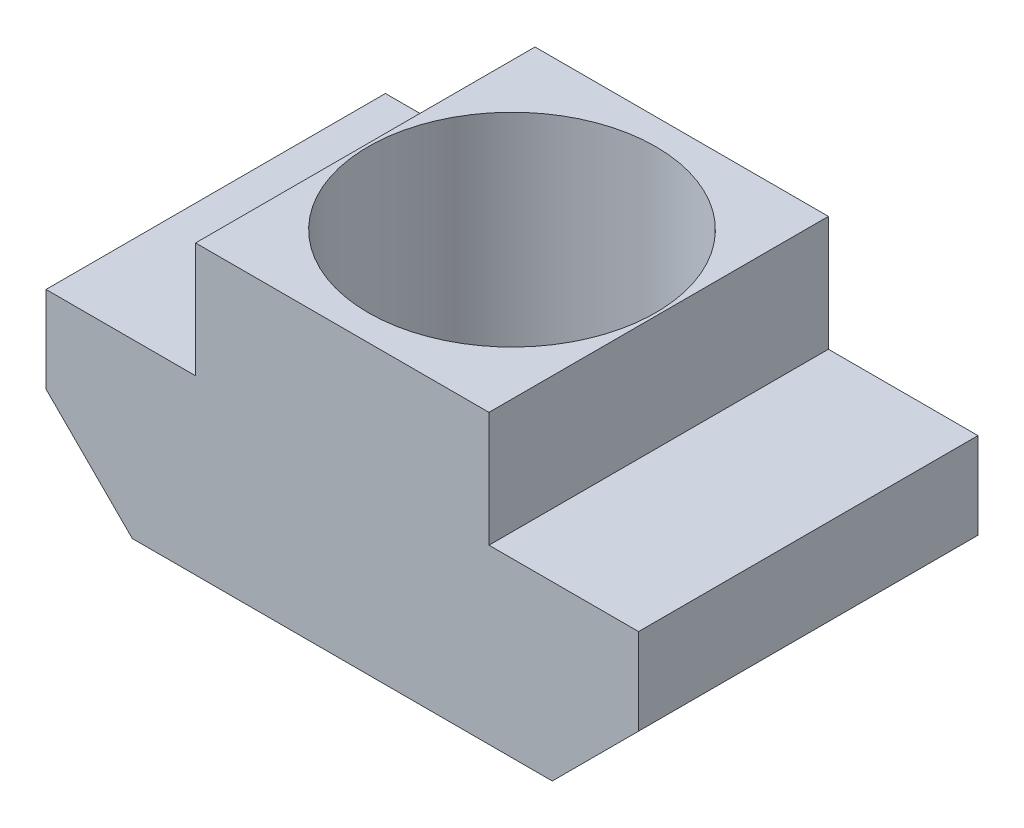
SolidWorks part; units mm, degrees
ref_plane "前视基准面" through (0, 0, 0) normal (0, 0, 1) x (1, 0, 0)
ref_plane "上视基准面" through (0, 0, 0) normal (0, 1, 0) x (1, 0, 0)
ref_plane "右视基准面" through (0, 0, 0) normal (1, 0, 0) x (0, 0, -1)
sketch "草图1" plane through (0, 0, 0) normal (0, 1, 0) x (1, 0, 0)
  line L1 (5.15, 2.95) -> (-5.15, 2.95)
  line L2 (5.15, 2.95) -> (5.15, -2.95)
  line L3 (5.15, -2.95) -> (-5.15, -2.95)
  line L4 (-5.15, 2.95) -> (-5.15, -2.95)
  line L5 (2.55, 2.95) -> (-2.55, 2.95)
  line L6 (2.55, 2.95) -> (2.55, -2.95)
  line L7 (2.55, -2.95) -> (-2.55, -2.95)
  line L8 (-2.55, 2.95) -> (-2.55, -2.95)
  line L9 (2.55, 2.95) -> (-2.55, -2.95) construction
  line L10 (2.55, -2.95) -> (-2.55, 2.95) construction
  circle A0 centre (0, 0) radius 2.5
  point P0 (0, 0)
  dimension "D3" = 5.9
  dimension "D1" = 10.3
  dimension "D2" = 5.9
  dimension "D4" = 5.1
extrude "凸台-拉伸3" add sketch "草图1" along normal blind 3 contours L8 L1 L4 L3 | L1 L6 L3 L2 region at (3.85, 0, 0) region at (-3.85, 0, 0)
extrude "凸台-拉伸4" add sketch "草图1<3>" along normal blind 5 contours L1 L8 L3 L6 A0 region at (2.5422, 0, 0)
sketch "草图1<3>" plane through (0, 0, 0) normal (0, 1, 0) x (1, 0, 0) same geometry as "草图1"
sketch "草图2" plane through (0, 0, 2.95) normal (0, 0, 1) x (1, 0, 0)
  line L0 (-5.15, 3) -> (-5.15, 0) construction
  line L1 (-5.15, 1.5) -> (-3.65, 0)
  line L2 (5.15, 0) -> (-5.15, 0) construction
  line L3 (5.15, 1.5) -> (3.65, 0)
  line L4 (5.15, 3) -> (5.15, 0) construction
  line L5 (3.65, 0) -> (5.15, 0)
  line L6 (5.15, 0) -> (5.15, 1.5)
  line L7 (-3.65, 0) -> (-5.15, 0)
  line L8 (-5.15, 0) -> (-5.15, 1.5)
extrude "切除-拉伸1" cut sketch "草图2" against normal through all
